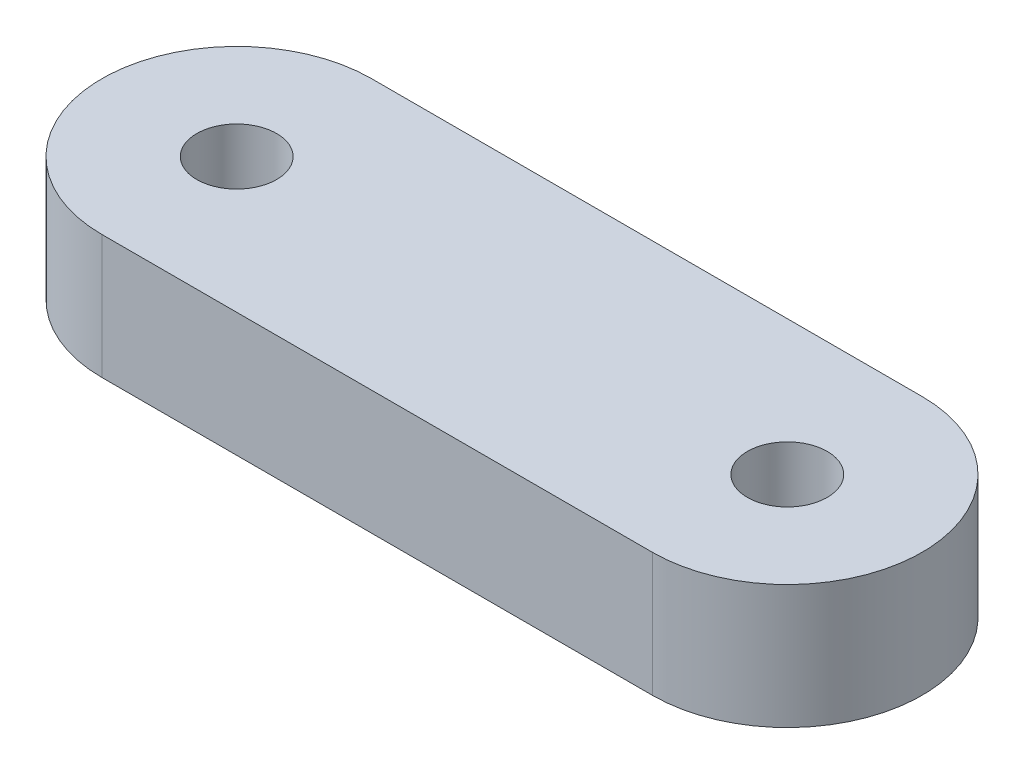
SolidWorks part; units mm, degrees
ref_plane "Front Plane" through (0, 0, 0) normal (0, 0, 1) x (1, 0, 0)
ref_plane "Top Plane" through (0, 0, 0) normal (0, 1, 0) x (1, 0, 0)
ref_plane "Right Plane" through (0, 0, 0) normal (1, 0, 0) x (0, 0, -1)
sketch "Sketch1" plane through (0, 0, 0) normal (0, 1, 0) x (1, 0, 0)
  line L0 (14.9, 0) -> (14.9, 15.5804) construction
  line L1 (-10, 4.9) -> (10, 4.9)
  line L2 (-14.9, 0) -> (-14.9, 15.5804) construction
  line L3 (-10, -4.9) -> (10, -4.9)
  line L4 (-10, 4.9) -> (-10, -4.9) construction
  line L5 (-10, 4.9) -> (10, -4.9) construction
  line L6 (-10, -4.9) -> (10, 4.9) construction
  line L7 (10, 4.9) -> (10, -4.9) construction
  line L8 (0, 4.9) -> (0, -4.9) construction
  arc A0 (-10, 4.9) -> (-10, -4.9) centre (-10, 0) ccw
  arc A1 (10, -4.9) -> (10, 4.9) centre (10, 0) ccw
  circle A2 centre (-10, 0) radius 1.45
  circle A3 centre (10, 0) radius 1.45
  point P0 (0, 0)
  dimension "D4" = 4.9
  dimension "D5" = 2.9
  dimension "D1" = 9.8
  dimension "D2" = 20
extrude "Boss-Extrude1" add sketch "Sketch1" along normal blind 4.5
equation "\"Y-ROD-SPACING\"=75"
equation "\"Y-BED-OFFSET\"=2"
equation "\"Y-BED-ROD-INSET\"=3.5"
equation "\"T-SLOT-NUT-FILLET-RADIUS\"=0.5"
equation "\"T-SLOT-SCREW-SHAFT-RADIUS\"=1.55"
equation "\"T-SLOT-SCREW-SHAFT-CUTOUT-LENGTH\"=11"
equation "\"T-SLOT-NUT-DEPTH\"=3.5"
equation "\"T-SLOT-NUT-WIDTH\"=2.85"
equation "\"T-SLOT-NUT-END-DISTANCE\"=8"
equation "\"ACRYLIC-TAB-CUTOUT-SIZE\"=\"ACRYLIC-THICKNESS\"+\"ACRYLIC-TAB-TOLERANCE\"*2"
equation "\"ACRYLIC-M3-HOLE\"=2.9"
equation "\"D5@Sketch1\"=\"ACRYLIC-M3-HOLE\""
equation "\"SMOOTHROD-CAP-SCREW-DISTANCE\"=20"
equation "\"D2@Sketch1\"=\"SMOOTHROD-CAP-SCREW-DISTANCE\""
equation "\"X-ROD-SPACING\"=45"
equation "\"Z-ROD-SPACING\"=17.5"
equation "\"ACRYLIC-THICKNESS\"=10"
equation "\"ACRYLIC-THICKNESS2\"=4.5"
equation "\"ACRYLIC-TAB-WIDTH\"=\"ACRYLIC-THICKNESS\""
equation "\"FRAME-WIDTH-INNER\"=370"
equation "\"NEMA17-HOLE-SPACING\"=31"
equation "\"NEMA17-CENTRAL-CUTOUT\"=22.5"
equation "\"Z-BRACKET-REACH\"=57"
equation "\"TOP-BRACKET-SPACING\"=40"
equation "\"SMOOTHROD-X-LENGTH\"=350"
equation "\"SMOOTHROD-Y-LENGTH\"=350"
equation "\"SMOOTHROD-Z-LENGTH\"=350"
equation "\"SMOOTHROD-TIGHTENING-HEADROOM\"=.25"
equation "\"LEADSCREW-Z-LENGTH\"=300"
equation "\"SCREW-LENGTH-FRAME\"=\"ACRYLIC-THICKNESS\" + 10"
equation "\"SCREW-HEAD-RADIUS\"=6"
equation "\"PRINTED-X-SMOOTHROD-DIAMETER\"=8.8"
equation "\"PRINTED-X-SMOOTHROD-CUTOUT\"=10"
equation "\"PRINTED-X-BASE-HEIGHT\"=10"
equation "\"PRINTED-LM8UU-CUTOUT-SIZE\"=15.5"
equation "\"PRINTED-LM8UU-CUTOUT-LENGTH\"=24.5"
equation "\"PRINTED-X-IDLER-HEIGHT\"=16"
equation "\"PSU-MOUNTING-WIDTH\"=95"
equation "\"PSU-MOUNTING-HEIGHT\"=177"
equation "\"D1@Boss-Extrude1\"=\"ACRYLIC-THICKNESS2\""
